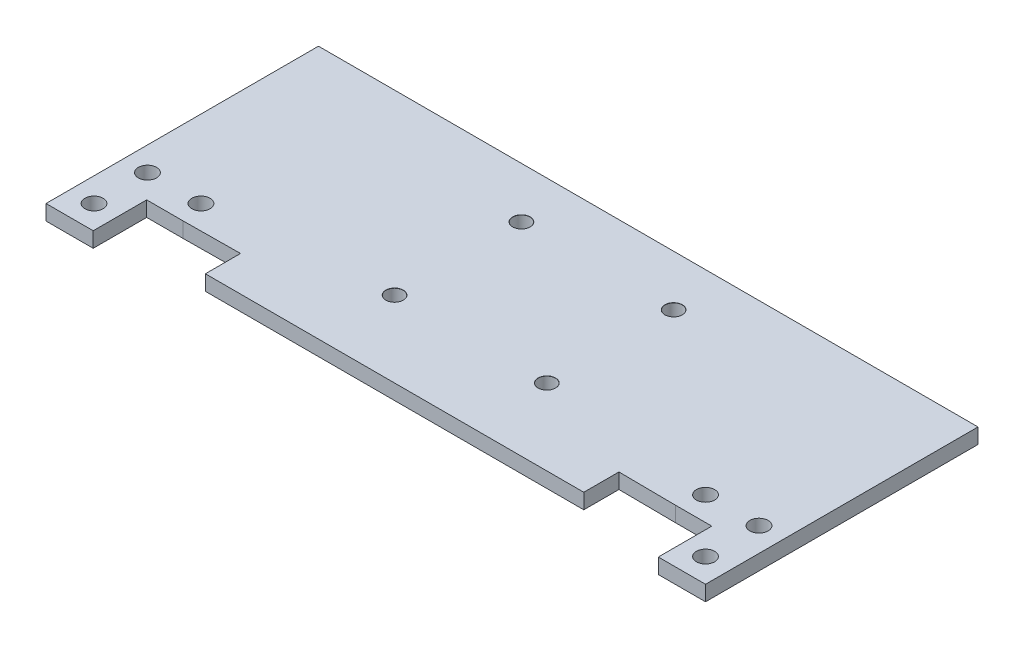
SolidWorks part; units mm, degrees
ref_plane "Front Plane" through (0, 0, 0) normal (0, 0, 1) x (1, 0, 0)
ref_plane "Top Plane" through (0, 0, 0) normal (0, 1, 0) x (1, 0, 0)
ref_plane "Right Plane" through (0, 0, 0) normal (1, 0, 0) x (0, 0, -1)
sketch "Sketch1" plane through (0, 0, 0) normal (1, 0, 0) x (0, 0, -1)
  line L2 (3.71, 3) -> (53.71, 3)
  line L6 (3.71, 0) -> (53.71, 0)
  line L7 (53.71, 0) -> (53.71, 3)
  line L8 (3.71, 3) -> (3.71, 0)
  dimension "D1" = 3.71
  dimension "D3" = 50
  dimension "D6" = 3
extrude "Boss-Extrude1" add sketch "Sketch1" along normal blind 130
hole_wizard "M3 Clearance Hole2" positions "Sketch5" profile "Sketch6" hole size "M3" standard "ANSI Metric" end condition through all
sketch "Sketch5" plane through (0, 3, 0) normal (0, 1, 0) x (1, 0, 0)
  line L0 (65, 53.71) -> (65, 43.71) construction
  line L1 (130, 53.71) -> (0, 53.71) construction
  line L3 (50, 43.71) -> (80, 43.71) construction
  line L4 (80, 43.71) -> (80, 18.71) construction
  line L5 (80, 18.71) -> (50, 18.71) construction
  line L6 (50, 18.71) -> (50, 43.71) construction
  point P9 (50, 43.71)
  point P11 (80, 43.71)
  point P13 (50, 18.71)
  point P15 (80, 18.71)
  point P25 (65, 43.71)
  dimension "D1" = 30
  dimension "D2" = 25
  dimension "D3" = 10
sketch "Sketch6" plane through (80, 3, -18.71) normal (1, 0, 0) x (0, 0, 1)
  line L0 (0, 0) -> (0, 3)
  line L1 (0, 3) -> (1.7, 3)
  line L2 (1.7, 3) -> (1.7, 0.025)
  line L3 (1.7, 0.025) -> (1.725, 0)
  line L5 (1.725, 0) -> (0, 0)
  line L6 (-1.7, 0.025) -> (-1.725, 0) construction
  line L11 (0, -6.35) -> (0, 107.95) construction
  dimension "Thru Hole Dia." = 3.4
  dimension "Thru Hole Depth" = 3
  dimension "Near C'Sink Dia." = 3.45
  dimension "Near C'Sink Angle" = 90
sketch "Sketch7" plane through (0, 0, 0) normal (0, -1, 0) x (1, 0, 0)
  line L0 (130, -3.71) -> (0, -3.71) construction
  line L1 (130, -3.71) -> (0, -3.71)
  line L2 (108.1956, -3.71) -> (108.1956, 0.0001)
  line L3 (108.1956, 0.0001) -> (130, 0.0001)
  line L4 (130, 13.0001) -> (130, -19.9999) construction
  line L5 (130, 0.0001) -> (130, -3.71)
  line L6 (125.2699, -4.73) -> (130, -4.73) construction
  line L7 (130, -3.71) -> (130, -53.71) construction
  line L8 (119.0978, 0.0001) -> (119.0978, -4.73) construction
  line L9 (120.4956, -10.3397) -> (120.4956, 4.3493) construction
  line L10 (120.4956, -10.3397) -> (120.4956, 4.3493) construction
  line L11 (65, -3.71) -> (65, -53.71) construction
  line L12 (130, -53.71) -> (0, -53.71) construction
  line L13 (0, 0.0001) -> (0, -3.71)
  line L14 (21.8044, 0.0001) -> (0, 0.0001)
  line L15 (21.8044, -3.71) -> (21.8044, 0.0001)
  circle A0 centre (125.2699, -4.73) radius 1.8 construction
  circle A1 centre (125.2699, -4.73) radius 1.8 construction
  line M17 (130, -3.71) -> (0, -3.71)
  dimension "D1" = 12.3
extrude "Boss-Extrude2" add sketch "Sketch7" against normal up to surface (3 mm away) contours L5 L3 L2 M17 | L15 L14 L13 M17 region at (10.9022, 0, -1.8549) region at (119.0978, 0, -1.8549) up to face at (50, 3, -41.985)
sketch "Sketch9" plane through (0, 3, 0) normal (0, 1, 0) x (1, 0, 0)
  line L0 (120.4956, 10.3397) -> (113.4956, 10.3397) construction
  line L1 (120.4956, 10.3397) -> (120.4956, -4.3493) construction
  line L2 (120.4956, 10.3397) -> (113.4956, 10.3397)
  line L3 (120.4956, 10.3397) -> (120.4956, -4.3493)
  line L4 (102.4956, 0.9897) -> (102.4956, 10.4376) construction
  line L5 (102.4956, 0.9897) -> (102.4956, 10.4376)
  line L6 (113.4956, 10.3397) -> (102.4956, 10.4376)
  line L7 (102.4956, 0.9897) -> (120.4956, -4.3493)
  line L8 (102.2956, 0.8404) -> (102.2956, 10.6394)
  line L9 (113.4965, 10.5397) -> (102.2956, 10.6394)
  line L10 (120.6956, 10.5397) -> (113.4965, 10.5397)
  line L11 (120.6956, 10.5397) -> (120.6956, -4.6173)
  line L12 (102.2956, 0.8404) -> (120.6956, -4.6173)
  line L13 (108.1956, 3.71) -> (21.8044, 3.71) construction
  line L14 (130, 53.71) -> (0, 53.71) construction
  line L15 (108.1956, 3.71) -> (21.8044, 3.71) construction
  line L16 (130, 53.71) -> (0, 53.71) construction
  line L17 (65, 53.71) -> (65, 3.71) construction
  line L18 (9.3044, 10.5397) -> (9.3044, -4.6173)
  line L19 (9.3044, 10.5397) -> (16.5035, 10.5397)
  line L20 (16.5035, 10.5397) -> (27.7044, 10.6394)
  line L21 (27.7044, 0.8404) -> (27.7044, 10.6394)
  line L22 (27.7044, 0.8404) -> (9.3044, -4.6173)
  line M8 (21.8044, -0.0001) -> (21.8044, 3.71)
  line M9 (21.8044, 3.71) -> (108.1956, 3.71)
  line M10 (108.1956, 3.71) -> (108.1956, -0.0001)
  dimension "D1" = 0.2
extrude "Cut-Extrude1" cut sketch "Sketch9" against normal through all contours L2 L6 L5 L3 M9 | L5 L7 L3 M9 | L8 L12 L11 L3 L7 L5 M10 M9 | L11 L10 L9 L8 L5 L6 L2 L3 M9 | L21 L20 L19 L18 M9 | L22 L21 L18 M9 M8 region at (112.147, 3, -4.2464) region at (102.3195, 3, -7.1747) region at (17.846, 3, -4.2412)
sketch "Sketch10" plane through (0, 3, 0) normal (0, 1, 0) x (1, 0, 0)
  point P0 (125.2699, 4.73)
  point P3 (125.2699, 15.2698)
  point P6 (114.7301, 15.2698)
hole_wizard "M3 Clearance Hole3" positions "Sketch10" profile "Sketch11" hole size "M3" standard "ANSI Metric" end condition through all
sketch "Sketch11" plane through (125.2699, 3, -4.73) normal (1, 0, 0) x (0, 0, 1)
  line L0 (0, 0) -> (0, 3)
  line L1 (0, 3) -> (1.8, 3)
  line L2 (1.8, 3) -> (1.8, 0)
  line L5 (1.8, 0) -> (0, 0)
  line L11 (0, -6.35) -> (0, 107.95) construction
  dimension "Thru Hole Dia." = 3.6
  dimension "Thru Hole Depth" = 3
ref_plane "Plane1" through (65, 0, 0) normal (1, 0, 0) x (0, 0, -1)
mirror "Mirror1" about plane through (65, 0, 0) normal (1, 0, 0) of "M3 Clearance Hole3"
